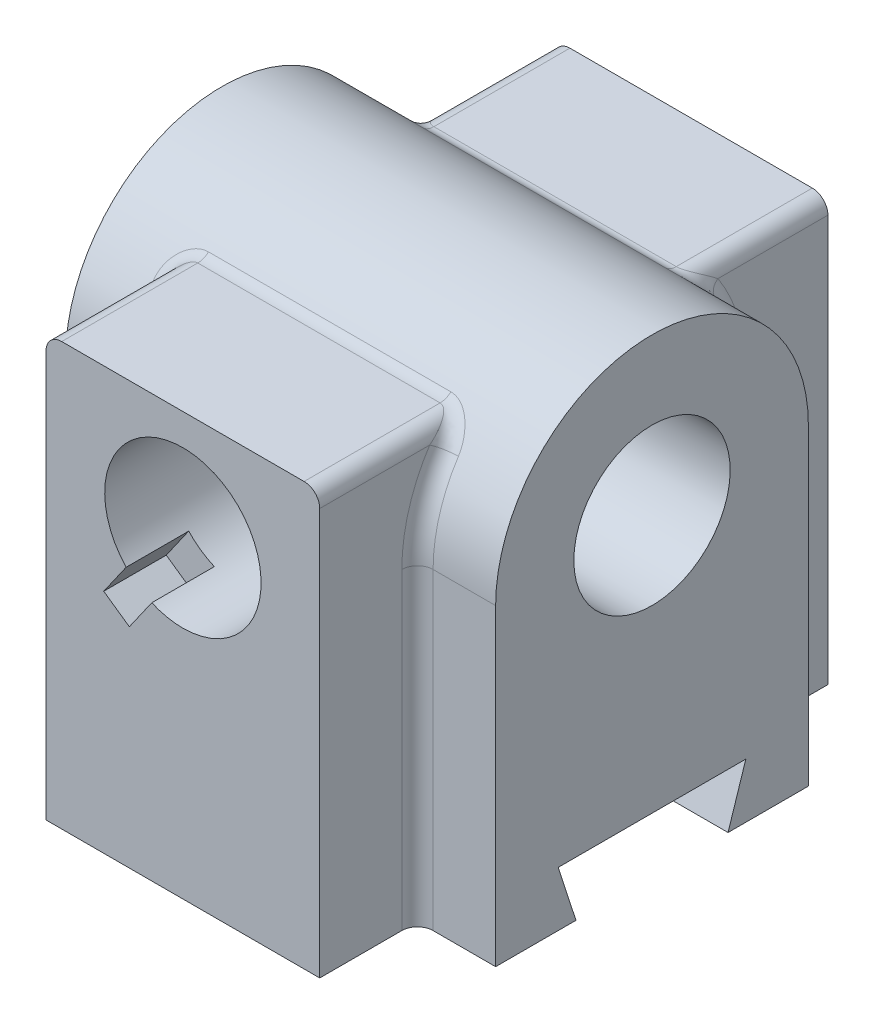
SolidWorks part; units mm, degrees
ref_plane "Front Plane" through (0, 0, 0) normal (0, 0, 1) x (1, 0, 0)
ref_plane "Top Plane" through (0, 0, 0) normal (0, 1, 0) x (1, 0, 0)
ref_plane "Right Plane" through (0, 0, 0) normal (1, 0, 0) x (0, 0, -1)
sketch "Sketch1" plane through (0, 0, 0) normal (1, 0, 0) x (0, 0, -1)
  line L0 (-20, 0) -> (-20, -40)
  line L1 (20, 0) -> (20, -40)
  line L6 (20, -40) -> (-20, -40)
  arc A1 (-20, 0) -> (20, 0) centre (0, 0) cw
  point P5 (13.7129, -33)
  point P8 (0, 0)
  dimension "D1" = 40
  dimension "D3" = 40
extrude "Boss-Extrude1" add sketch "Sketch1" along normal mid plane 55
sketch "Sketch2" plane through (0, 0, 0) normal (0, 0, 1) x (1, 0, 0)
  line L0 (27.5, 20) -> (-27.5, 20) construction
  line L1 (-17.5, 14) -> (17.5, 14)
  line L2 (-17.5, 14) -> (-17.5, -40)
  line L3 (-17.5, -40) -> (17.5, -40)
  line L4 (17.5, 14) -> (17.5, -40)
  dimension "D1" = 35
  dimension "D2" = 17.5
  dimension "D3" = 54
  dimension "D4" = 60
extrude "Boss-Extrude2" add sketch "Sketch2" along normal mid plane 65
sketch "Sketch5" plane through (27.5, 0, 0) normal (1, 0, 0) x (0, 0, -1)
  line L0 (-9.7256, -40) -> (-12, -33)
  line L1 (-12, -33) -> (12, -33)
  line L2 (12, -33) -> (9.7256, -40)
  line L3 (9.7256, -40) -> (-9.7256, -40)
  line L4 (-20, -40) -> (20, -40) construction
  circle A0 centre (0, 0) radius 10
  point P7 (3.89, -43.4322)
  point P10 (12.2573, -33)
  dimension "D1" = 20
  dimension "D2" = 24
  dimension "D3" = 72
  dimension "D4" = 72
  dimension "D5" = 7
  dimension "D6" = 12
extrude "Cut-Extrude1" cut sketch "Sketch5" against normal through all both and the other way through all
sketch "Sketch6" plane through (0, 0, 32.5) normal (0, 0, 1) x (1, 0, 0)
  circle A0 centre (0, 0) radius 10
  dimension "D1" = 20
extrude "Cut-Extrude2" cut sketch "Sketch6" against normal through all both
sketch "Sketch7" plane through (0, 0, 32.5) normal (0, 0, 1) x (1, 0, 0)
  line L0 (0, 0) -> (-9.7505, -13.9252) construction
  line L1 (-7.2582, -6.8789) -> (-10.1261, -10.9746)
  line L2 (-10.1261, -10.9746) -> (-6.8495, -13.2689)
  line L3 (-6.8495, -13.2689) -> (-3.9816, -9.1732)
  line L4 (-3.9816, -9.1732) -> (-7.2582, -6.8789)
  line L5 (0, 0) -> (0, -3.8636) construction
  circle A0 centre (0, 0) radius 10 construction
  dimension "D1" = 4
  dimension "D2" = 5
  dimension "D3" = 35
extrude "Cut-Extrude3" cut sketch "Sketch7" against normal blind 8
fillet "Fillet1" radius 2 14 edges at (17.5, -20, -20) (17.5, -20, 20) (17.5, 7.5612, -18.5156) (17.5, 7.5612, 18.5156) (0, 14, -14.2829) (0, 14, 14.2829) (-17.5, 7.5612, -18.5156) (-17.5, 7.5612, 18.5156) (-17.5, -20, -20) (-17.5, -20, 20) (-17.5, 14, -23.3914) (17.5, 14, -23.3914) (-17.5, 14, 23.3914) (17.5, 14, 23.3914)
equation "\"D2@Sketch2\"=\"D1@Sketch2\"/2"
equation "\"D4@Sketch5\"=\"D3@Sketch5\""
equation "\"D6@Sketch5\"=\"D2@Sketch5\"/2"
